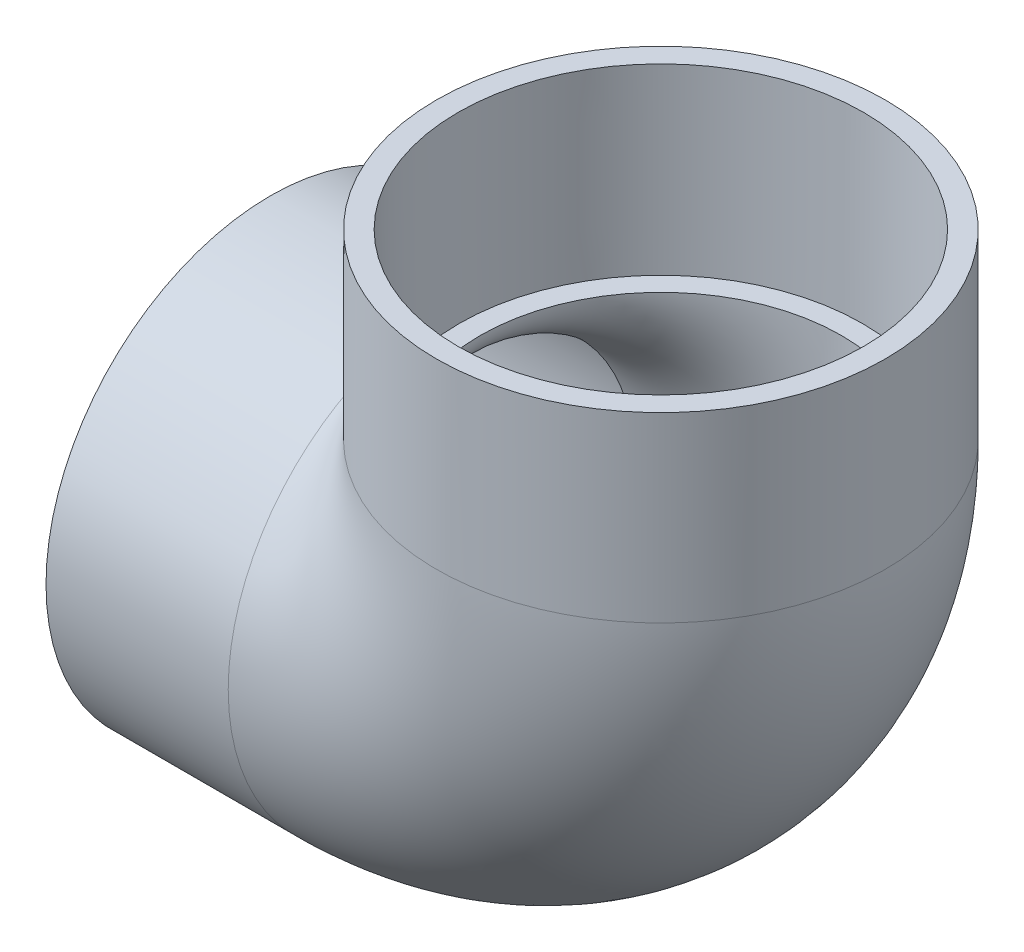
SolidWorks part; units mm, degrees
material "PVC Rigid"
ref_plane "Front Plane" through (0, 0, 0) normal (0, 0, 1) x (1, 0, 0)
ref_plane "Top Plane" through (0, 0, 0) normal (0, 1, 0) x (1, 0, 0)
ref_plane "Right Plane" through (0, 0, 0) normal (1, 0, 0) x (0, 0, -1)
sketch "Sketch0" plane through (0, 0, 0) normal (0, 0, 1) x (1, 0, 0)
  line L0 (-110.49, 0) -> (0, 0) construction
  line L1 (0, 0) -> (0, 110.49) construction
  line L2 (-58.928, 0) -> (0, 0) construction
  line L3 (0, 0) -> (0, 58.928) construction
  line L4 (-110.49, 63.5) -> (-110.49, -63.5) construction
  line L5 (-58.928, 57.0357) -> (-110.49, 57.3786) construction
  line L6 (-58.928, 57.0357) -> (-58.928, -57.0357) construction
  line L7 (-58.928, -57.0357) -> (-110.49, -57.3786) construction
  line L8 (-110.49, 57.3786) -> (-110.49, -57.3786) construction
  line L9 (-63.5, 110.49) -> (63.5, 110.49) construction
  line L10 (-57.3786, 110.49) -> (57.3786, 110.49) construction
  line L11 (57.3786, 110.49) -> (57.0357, 58.928) construction
  line L12 (57.0357, 58.928) -> (-57.0357, 58.928) construction
  line L13 (-57.0357, 58.928) -> (-57.3786, 110.49) construction
  line L14 (-58.928, 51.1302) -> (-58.928, -51.1302) construction
  line L18 (-51.1302, 58.928) -> (51.1302, 58.928) construction
  dimension "H" = 110.49
  dimension "G" = 58.928
  dimension "M" = 127
  dimension "OD A" = 114.7572
  dimension "OD B" = 114.0714
  dimension "ID" = 102.2604
sketch "Sketch1" plane through (0, 0, 0) normal (0, 0, 1) x (1, 0, 0)
  line L0 (-110.49, 0) -> (0, 0) construction
  line L1 (-110.49, 0) -> (0, 0) construction
  line L3 (-110.49, -63.5) -> (-58.928, -63.5)
  line L4 (-110.49, -63.5) -> (-110.49, -57.3786)
  line L5 (-110.49, -57.3786) -> (-58.928, -57.0357)
  line L6 (-58.928, -63.5) -> (-58.928, -57.0357)
revolve "Revolve1" add sketch "Sketch1" angle 360 about L1
sketch "Sketch2" plane through (0, 0, 0) normal (0, 0, 1) x (1, 0, 0)
  line L0 (57.3786, 110.49) -> (57.0357, 58.928)
  line L1 (57.0357, 58.928) -> (63.5, 58.928)
  line L2 (63.5, 58.928) -> (63.5, 110.49)
  line L3 (63.5, 110.49) -> (57.3786, 110.49)
  line L4 (0, 0) -> (0, 110.49) construction
  line L5 (0, 0) -> (0, 110.49) construction
revolve "Revolve2" add sketch "Sketch2" angle 360 about L5
sketch "Sketch3" plane through (-58.928, 0, 0) normal (1, 0, 0) x (0, 0, -1)
  circle A0 centre (0, 0) radius 51.1302
  circle A1 centre (0, 0) radius 63.5
sketch "Sketch4" plane through (0, 0, 0) normal (0, 0, 1) x (1, 0, 0)
  line L0 (-110.49, 0) -> (0, 0) construction
  line L1 (0, 0) -> (0, 110.49) construction
  line L2 (-110.49, 0) -> (-58.928, 0) construction
  line L3 (0, 58.928) -> (0, 110.49) construction
  arc A0 (-58.928, 0) -> (0, 58.928) centre (-58.928, 58.928) ccw
sweep "Sweep1" add profiles "Sketch3" path "Sketch4"
